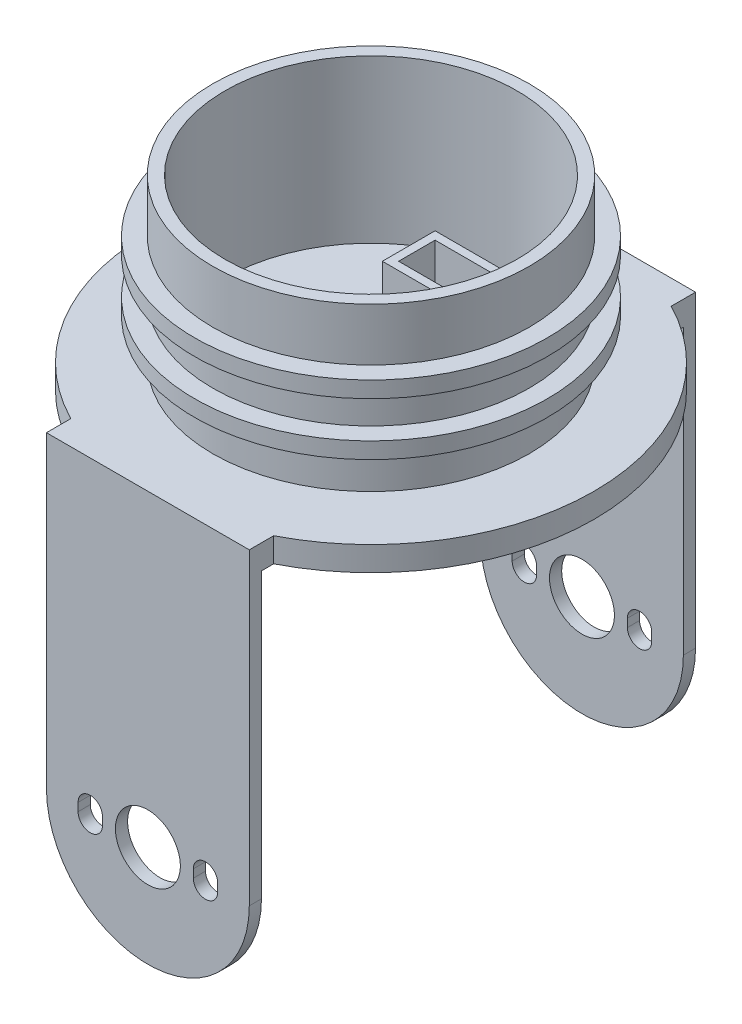
SolidWorks part; units mm, degrees
ref_plane "前基準面" through (0, 0, 0) normal (0, 0, 1) x (1, 0, 0)
ref_plane "上基準面" through (0, 0, 0) normal (0, 1, 0) x (1, 0, 0)
ref_plane "右基準面" through (0, 0, 0) normal (1, 0, 0) x (0, 0, -1)
sketch "草圖1" plane through (0, 0, 0) normal (0, 1, 0) x (1, 0, 0)
  circle A0 centre (0, 0) radius 19.5
  circle A1 centre (0, 0) radius 18
  dimension "D1" = 39
  dimension "D2" = 36
extrude "填料-伸長1" add sketch "草圖1" along normal blind 20
sketch "草圖3" plane through (0, 0, 0) normal (0, -1, 0) x (1, 0, 0)
  circle A0 centre (0, 0) radius 27.5
  dimension "D1" = 55
extrude "填料-伸長2" add sketch "草圖3" along normal blind 3
ref_plane "平面2" through (0, -3, 0) normal (0, -1, 0) x (-1, 0, 0)
ref_plane "平面5" through (0, 0, 0) normal (0, 1, 0) x (1, 0, 0)
ref_plane "平面6" through (0, 7, 0) normal (0, -1, 0) x (-1, 0, 0)
sketch "草圖25" plane through (0, 7, 0) normal (0, -1, 0) x (-1, 0, 0)
  circle A0 centre (0, 0) radius 21.75
  circle A1 centre (0, 0) radius 19.5
  dimension "D1" = 43.5
extrude "填料-伸長12" add sketch "草圖25" along normal blind 2
ref_plane "平面10" through (0, 10.5, 0) normal (0, -1, 0) x (-1, 0, 0)
sketch "草圖26" plane through (0, 10.5, 0) normal (0, -1, 0) x (-1, 0, 0)
  circle A0 centre (0, 0) radius 21.75
  circle A1 centre (0, 0) radius 19.5
extrude "填料-伸長13" add sketch "草圖26" against normal blind 2 from offset 1 offset against normal yes
sketch "草圖27" plane through (0, -3, 0) normal (0, -1, 0) x (1, 0, 0)
  line L0 (0, 0) -> (-12.5, 0)
  line L1 (46.0389, 0) -> (-46.0389, 0) construction
  line L2 (-12.5, 0) -> (-12.5, 27.5)
  line L3 (-12.5, 27.5) -> (12.5, 27.5)
  line L4 (12.5, 27.5) -> (12.5, 0)
  line L5 (12.5, 0) -> (-12.5, 0)
  line L6 (-12.5, 0) -> (-12.5, -26)
  line L7 (-12.5, -26) -> (12.5, -26)
  line L8 (12.5, -26) -> (12.5, 0)
  circle M6 centre (0, 0) radius 27.5
  dimension "D1" = 26
  dimension "D2" = 27.5
extrude "填料-伸長14" add sketch "草圖27" against normal blind 3 contours L8 L5 L0 L6 L7 M6 | L5 L4 L3 L2 L0 M6 | L6 L7 M6 | L7 L8 M6 | L4 L3 M6 | L3 L2 M6 region at (0, -3, -12.9033) region at (0, -3, 13.2755) region at (-9.4102, -3, 26.6076) region at (-11.3596, -3, -25.514) region at (9.4102, -3, 26.6076) region at (11.3596, -3, -25.514)
sketch "草圖28" plane through (0, 0, -26) normal (0, 0, -1) x (-1, 0, 0)
  line L0 (12.5, -3) -> (12.5, -38)
  line L1 (12.5, -38) -> (-12.5, -38)
  line L2 (-12.5, -38) -> (-12.5, 0)
  line L3 (-12.5, 0) -> (12.5, 0)
  line L4 (12.5, 0) -> (12.5, -3) construction
  line L5 (12.5, 0) -> (12.5, -3)
  line L6 (-7.1, -37.5) -> (-7.1, -38.5) construction
  line L7 (-5.6, -37.5) -> (-5.6, -38.5)
  line L8 (-8.6, -37.5) -> (-8.6, -38.5)
  line L9 (12.5, -3) -> (-12.5, -3)
  line L10 (7.1, -37.5) -> (7.1, -38.5) construction
  line L11 (8.6, -37.5) -> (8.6, -38.5)
  line L12 (5.6, -37.5) -> (5.6, -38.5)
  arc A0 (12.5, -38) -> (-12.5, -38) centre (0, -38) cw
  circle A1 centre (0, -38) radius 4
  arc A2 (-5.6, -37.5) -> (-8.6, -37.5) centre (-7.1, -37.5) ccw
  arc A3 (-8.6, -38.5) -> (-5.6, -38.5) centre (-7.1, -38.5) ccw
  arc A4 (8.6, -37.5) -> (5.6, -37.5) centre (7.1, -37.5) ccw
  arc A5 (5.6, -38.5) -> (8.6, -38.5) centre (7.1, -38.5) ccw
  point P14 (-7.1, -38)
  point P19 (-7.1, -36)
  point P20 (-7.1, -40)
  point P26 (7.1, -38)
  point P31 (7.1, -36)
  point P32 (7.1, -40)
  line M17 (8.9582, 0) -> (8.9582, -3)
  line M18 (8.9582, -3) -> (12.5, -3)
  line M19 (12.5, -3) -> (12.5, 0)
  line M20 (12.5, 0) -> (8.9582, 0)
  dimension "D1" = 8
  dimension "D2" = 4
  dimension "D3" = 3
  dimension "D4" = 5.6
  dimension "D5" = 4
  dimension "D6" = 3
  dimension "D7" = 5.6
  dimension "D8" = 35
extrude "填料-伸長17" add sketch "草圖28" along normal blind 1.5 contours A4 L11 L1 L0 L9 L2 L8 A2 L7 A1 L12 M18 | L9 L3 L2 M17 | M20 M17 M18 M19 | A5 L12 L1 A1 L7 A3 L8 A0 L11 region at (-10.7291, -1.5, -26) region at (0, -19.8277, -26) region at (0, -43.9487, -26) region at (1.7709, -1.5, -26)
extrude "填料-伸長25" add sketch "草圖28<25>" against normal blind 53.5 contours A4 L11 L1 L0 L9 L2 L8 A2 L7 A1 L12 M18 | A5 L12 L1 A1 L7 A3 L8 A0 L11 region at (0, -19.8277, -26) region at (0, -43.9487, -26)
sketch "草圖28<25>" plane through (0, 0, -26) normal (0, 0, -1) x (-1, 0, 0) same geometry as "草圖28"
sketch "草圖38" plane through (0, 0, -27.5) normal (0, 0, -1) x (-1, 0, 0)
  line L0 (-28.6, -3) -> (28.6, -3) construction
  line L1 (0, -9.8) -> (-1, -14.4947) construction
  line L2 (-1, -14.4947) -> (-1.3125, -15.9618) construction
  line L3 (0, 0) -> (0, -50.5) construction
  line L4 (0, -9.8) -> (1, -14.4947) construction
  line L5 (1, -14.4947) -> (1.3125, -15.9618) construction
  line L6 (-1, -14.4947) -> (-1.3125, -15.9618)
  line L7 (1, -14.4947) -> (1.3125, -15.9618)
  arc A0 (-12.5, -38) -> (12.5, -38) centre (0, -38) ccw construction
  circle A2 centre (0, -9.8) radius 4.8
  circle A3 centre (0, -9.8) radius 6.3
  arc A4 (1, -14.4947) -> (-1, -14.4947) centre (0, -9.8) ccw
  dimension "D1" = 6.8
  dimension "D2" = 9.6
  dimension "D3" = 12.6
  dimension "D4" = 2
  dimension "D5" = 1
extrude "除料-伸長15" cut sketch "草圖28<27>" against normal blind 52 contours A5 L12 L1 A1 L7 A3 L8 A0 L11 | A4 L11 L1 L0 L9 L2 L8 A2 L7 A1 L12 M18 region at (0, -19.8277, -26) region at (0, -43.9487, -26)
sketch "草圖28<27>" plane through (0, 0, -26) normal (0, 0, -1) x (-1, 0, 0) same geometry as "草圖28"
extrude "填料-伸長24" add sketch "草圖38<4>" along normal blind 3 contours L7 A3 L6 A2 region at (1.3296, -15.1913, -27.5)
sketch "草圖38<4>" plane through (0, 0, -27.5) normal (0, 0, -1) x (-1, 0, 0) same geometry as "草圖38"
extrude "填料-伸長23" add sketch "草圖38" against normal blind 8 contours L7 A3 L6 A2 | L6 A3 L7 A2 region at (0, -15.3429, -27.5) region at (1.3296, -15.1913, -27.5)
extrude "除料-伸長10" cut sketch "草圖38<3>" against normal blind 9.5 contours A2 region at (0, -9.8, -27.5)
sketch "草圖38<3>" plane through (0, 0, -27.5) normal (0, 0, -1) x (-1, 0, 0) same geometry as "草圖38"
sketch "草圖34" plane through (0, 0, 0) normal (0, 1, 0) x (1, 0, 0)
  line L0 (0, 0) -> (-17.3838, 0) construction
  line L1 (-17.3838, 0) -> (19.1481, 0) construction
  line L2 (0, 0) -> (0, -21.2728) construction
  line L3 (0, -21.2728) -> (0, 19.1859) construction
  line L4 (5.1, 13) -> (-5.1, 13) construction
  line L5 (-4.1, 12) -> (4.1, 12)
  line L6 (-4.1, 12) -> (-4.1, 7.5)
  line L7 (-4.1, 7.5) -> (4.1, 7.5)
  line L8 (4.1, 12) -> (4.1, 7.5)
  line L10 (5.1, 6.5) -> (-5.1, 6.5)
  line L11 (5.1, 6.5) -> (5.1, 13)
  line L12 (5.1, 13) -> (-5.1, 13)
  line L13 (-5.1, 6.5) -> (-5.1, 13)
  point P13 (0, 13)
  dimension "D1" = 8.2
  dimension "D2" = 4.5
  dimension "D3" = 1
  dimension "D4" = 12
  dimension "D5" = 1
  dimension "D6" = 1
  dimension "D7" = 1
extrude "填料-伸長22" add sketch "草圖34" along normal blind 5
sketch "草圖37" plane through (0, 0, 0) normal (0, 1, 0) x (1, 0, 0)
  line L2 (-4.1, 12) -> (4.1, 12)
  line L3 (-4.1, 12) -> (-4.1, 7.5)
  line L4 (-4.1, 7.5) -> (4.1, 7.5)
  line L5 (4.1, 12) -> (4.1, 7.5)
extrude "除料-伸長9" cut sketch "草圖37" against normal blind 5
